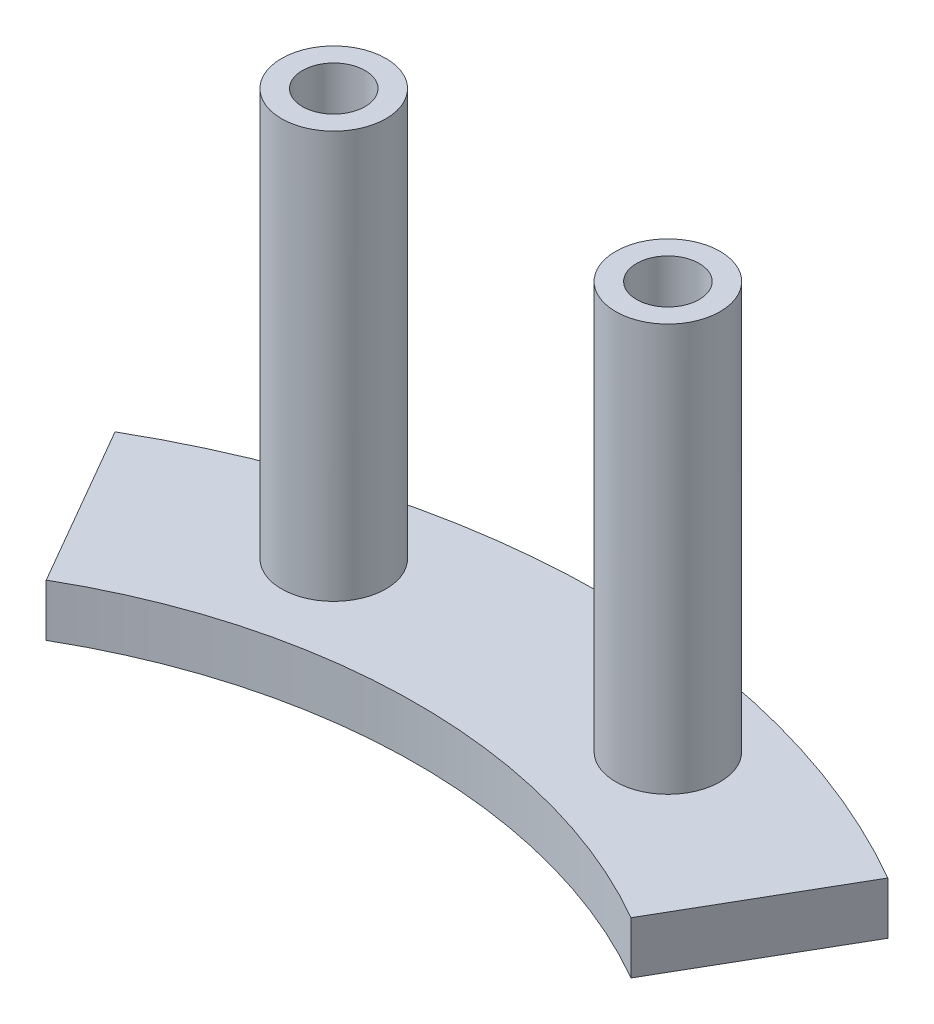
SolidWorks part; units mm, degrees
ref_plane "Front Plane" through (0, 0, 0) normal (0, 0, 1) x (1, 0, 0)
ref_plane "Top Plane" through (0, 0, 0) normal (0, 1, 0) x (1, 0, 0)
ref_plane "Right Plane" through (0, 0, 0) normal (1, 0, 0) x (0, 0, -1)
sketch "Sketch1" plane through (0, 0, 0) normal (0, 1, 0) x (1, 0, 0)
  line L0 (-14, 24.2487) -> (-18.5, 32.0429) construction
  line L1 (14, 24.2487) -> (18.5, 32.0429) construction
  line L2 (0, 0) -> (4, 0) construction
  line L3 (-18.5, 32.0429) -> (-14, 24.2487)
  line L4 (18.5, 32.0429) -> (14, 24.2487)
  circle A0 centre (0, 0) radius 28 construction
  circle A1 centre (0, 0) radius 37 construction
  arc A2 (-18.5, 32.0429) -> (18.5, 32.0429) centre (0, 0) cw
  arc A3 (-14, 24.2487) -> (14, 24.2487) centre (0, 0) cw
  arc A4 (-16.25, 28.1458) -> (16.25, 28.1458) centre (0, 0) cw construction
  dimension "D1" = 28
  dimension "D2" = 37
  dimension "D6" = 60
  dimension "D3" = 60
extrude "Boss-Extrude1" add sketch "Sketch1" along normal blind 2.5
sketch "Sketch2" plane through (0, 2.5, 0) normal (0, 1, 0) x (1, 0, 0)
  line L1 (14, 24.2487) -> (18.5, 32.0429) construction
  line L2 (-8, 32.0156) -> (8, 32.0156) construction
  line L3 (0, 32.0156) -> (0, 0) construction
  line L5 (-18.5, 32.0429) -> (-14, 24.2487) construction
  arc A0 (-16.5, 28.5788) -> (16.5, 28.5788) centre (0, 0) cw construction
  circle A1 centre (-8, 32.0156) radius 2.5
  circle A2 centre (8, 32.0156) radius 2.5
  dimension "D1" = 5
  dimension "D4" = 33
  dimension "D2" = 8
  dimension "D3" = 32.0156
extrude "Boss-Extrude2" add sketch "Sketch2" along normal blind 19.5
sketch "Sketch5" plane through (0, 22, 0) normal (0, 1, 0) x (1, 0, 0)
  circle A0 centre (-8, 32.0156) radius 1.5
  circle A2 centre (8, 32.0156) radius 1.5
  dimension "D1" = 3
extrude "Cut-Extrude1" cut sketch "Sketch5" against normal blind 3.5
